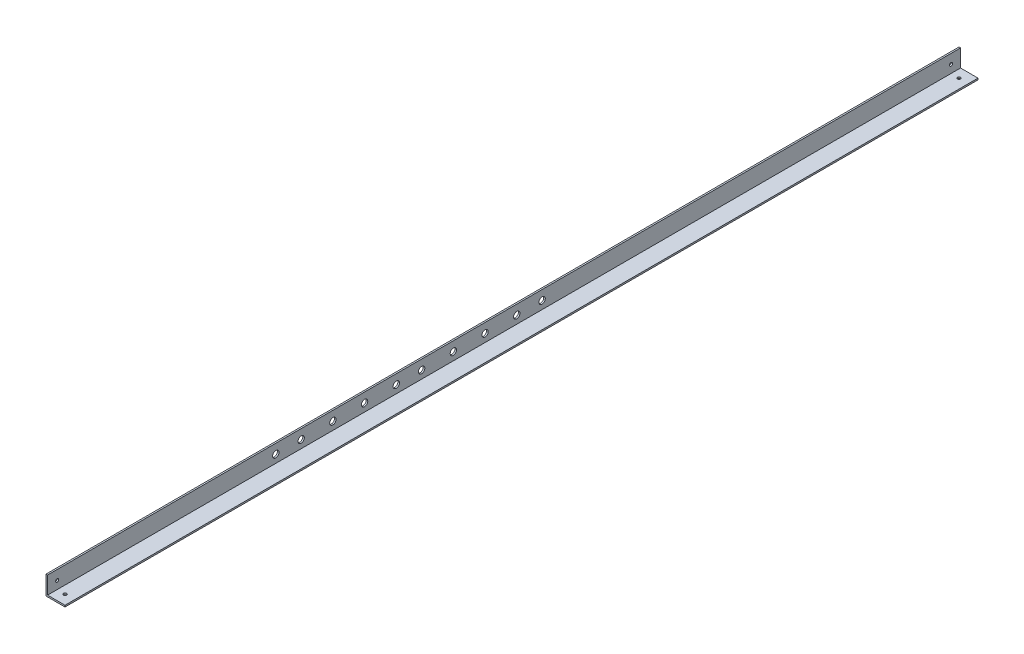
SolidWorks part; units mm, degrees
material "1060 Alloy"
ref_plane "Front Plane" through (0, 0, 0) normal (0, 0, 1) x (1, 0, 0)
ref_plane "Top Plane" through (0, 0, 0) normal (0, 1, 0) x (1, 0, 0)
ref_plane "Right Plane" through (0, 0, 0) normal (1, 0, 0) x (0, 0, -1)
sketch "Sketch1" plane through (0, 0, 0) normal (0, 0, 1) x (1, 0, 0)
  line L0 (0, 0) -> (0, 19.05)
  line L1 (0, 0) -> (19.05, 0)
  line L2 (0, 19.05) -> (1.5875, 19.05)
  line L3 (19.05, 0) -> (19.05, 1.5875)
  line L4 (19.05, 1.5875) -> (1.5875, 1.5875)
  line L5 (1.5875, 1.5875) -> (1.5875, 19.05)
  dimension "D1" = 19.05
  dimension "D2" = 19.05
  dimension "D3" = 1.5875
  dimension "D4" = 1.5875
extrude "Boss-Extrude1" add sketch "Sketch1" against normal blind 914.4
ref_axis "Axis1" through (0, 0, 0) along (0.7071, 0.7071, 0)
ref_plane "Plane1" through (0, 0, 0) normal (-0.7071, 0.7071, 0) x (0.7071, 0.7071, 0)
sketch "Sketch2" plane through (0, 1.5875, 0) normal (0, 1, 0) x (1, 0, 0)
  line L0 (1.5875, 914.4) -> (19.05, 914.4) construction
  line L1 (19.05, 0) -> (1.5875, 0) construction
  line L4 (9.525, -1000) -> (9.525, 49000) construction
  line L5 (1.5875, 0) -> (9.525, 0)
  circle A0 centre (9.525, 9.525) radius 1.5875
  circle A2 centre (9.525, 904.875) radius 1.5875
  dimension "D1" = 9.525
  dimension "D2" = 3.175
  dimension "D3" = 9.525
  dimension "D4" = 3.175
  dimension "D9" = 7.9375
extrude "Cut-Extrude2" cut sketch "Sketch2" against normal blind 2.794 contours A0 | A2
sketch "Sketch4" plane through (1.5875, 0, 0) normal (1, 0, 0) x (0, 0, -1)
  line L0 (914.4, 1.5875) -> (914.4, 9.525)
  line L1 (0, 19.05) -> (0, 0) construction
  line L2 (904.875, 9.525) -> (752.475, 9.525) construction
  line L3 (914.4, 9.525) -> (904.875, 9.525) construction
  line L5 (914.4, 1.5875) -> (914.4, 19.05) construction
  line L6 (0, 1.5875) -> (0, 19.05) construction
  circle A0 centre (9.525, 9.525) radius 1.5875
  circle A2 centre (904.875, 9.525) radius 1.5875
  circle A3 centre (254, 9.525) radius 3.175
  circle A4 centre (285.75, 9.525) radius 3.175
  circle A5 centre (317.5, 9.525) radius 3.175
  circle A6 centre (349.25, 9.525) radius 3.175
  circle A7 centre (469.9, 9.525) radius 3.175
  circle A8 centre (406.4, 9.525) radius 3.175
  circle A9 centre (438.15, 9.525) radius 3.175
  circle A10 centre (374.65, 9.525) radius 3.175
  dimension "D1" = 9.525
  dimension "D2" = 3.175
  dimension "D3" = 7.9375
  dimension "D4" = 3.175
  dimension "D8" = 31.75
  dimension "D6" = 6.35
  dimension "D10" = 120.65
  dimension "D11" = 31.75
  dimension "D12" = 31.75
  dimension "D13" = 31.75
  dimension "D14" = 254
  dimension "D5" = 9.525
  dimension "D7" = 31.75
  dimension "D9" = 31.75
extrude "Cut-Extrude3" cut sketch "Sketch4" against normal blind 8.89 contours A2 | A0 | A3 | A4 | A5 | A6 | A10 | A8 | A9 | A7
mirror "Mirror1" about plane through (0, 19.05, -914.4) normal (0, 1, 0) of "Cut-Extrude3", "Cut-Extrude2", "Boss-Extrude1"
ref_plane "Plane2" through (0, 19.05, 0) normal (0, -1, 0) x (-1, 0, 0)
sketch "Sketch10" plane through (0, 19.05, 0) normal (0, -1, 0) x (-1, 0, 0)
  line L1 (0, 914.4) -> (-19.05, 914.4)
  line L2 (0, 914.4) -> (0, 0)
  line L3 (0, 0) -> (-19.05, 0)
  line L4 (-19.05, 914.4) -> (-19.05, 0)
extrude "Cut-Extrude4" cut sketch "Sketch10" against normal through all
sketch "Sketch11" plane through (0, 0, 0) normal (-1, 0, 0) x (0, 0, 1)
  circle A0 centre (-228.6, 9.525) radius 3.175
  circle A1 centre (-495.3, 9.525) radius 3.175
extrude "Cut-Extrude5" cut sketch "Sketch11" against normal up to next
